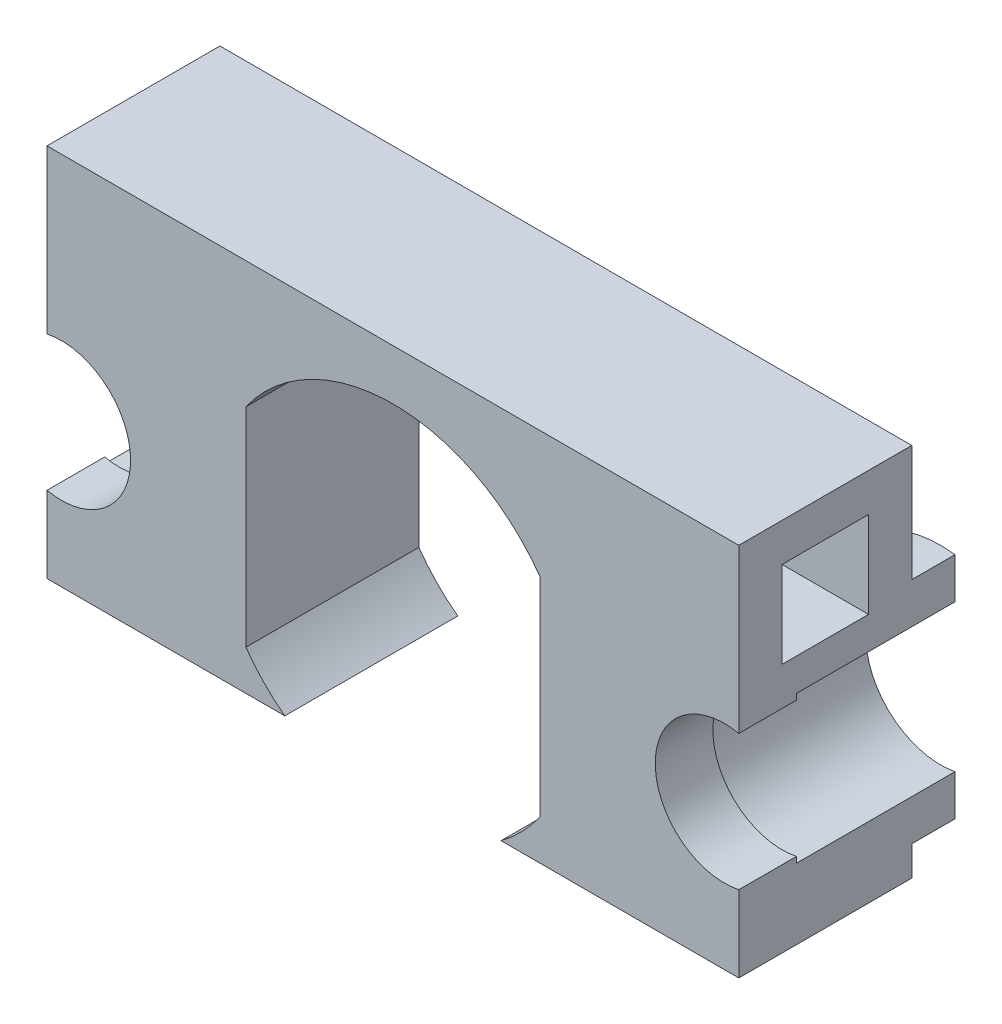
SolidWorks part; units mm, degrees
note: The reader was unsure of these and kept them because the rebuilt part matched: shared geometry of "Sketch17<2>", "Sketch19<3>".
ref_plane "Front Plane" through (0, 0, 0) normal (0, 0, 1) x (1, 0, 0)
ref_plane "Top Plane" through (0, 0, 0) normal (0, 1, 0) x (1, 0, 0)
ref_plane "Right Plane" through (0, 0, 0) normal (1, 0, 0) x (0, 0, -1)
sketch "Sketch1" plane through (0, 0, 0) normal (0, 0, 1) x (1, 0, 0)
  line L0 (-11.5, 0) -> (11.5, 0) construction
  line L1 (3.75, -5) -> (14.7, -5)
  line L2 (-14.7, -5) -> (-3.75, -5)
  line L3 (-14.7, -5) -> (-14.7, 8)
  line L4 (-14.7, 8) -> (14.7, 8)
  line L5 (14.7, -5) -> (14.7, 8)
  line L6 (-17.6832, -10.5909) -> (24.7009, -10.5909)
  line L7 (-24.9768, -7) -> (25.0232, -7) construction
  line L8 (-24.9768, -7) -> (-24.9768, -5) construction
  line L9 (-24.9768, -5) -> (-3.75, -5) construction
  line L10 (25.0232, -7) -> (25.0232, -5) construction
  line L11 (-24.9768, -7) -> (25.0232, -5) construction
  line L12 (-24.9768, -5) -> (25.0232, -7) construction
  line L13 (-5.1, -3.6128) -> (-5.1, 3.6128)
  line L14 (9, -3) -> (14, -3) construction
  line L15 (9, -3) -> (9, 3) construction
  line L16 (9, 3) -> (14, 3) construction
  line L17 (14, -3) -> (14, 3) construction
  line L18 (9, -3) -> (14, 3) construction
  line L19 (9, 3) -> (14, -3) construction
  line L20 (5.1, -3.6128) -> (5.1, 3.6128)
  line L21 (-5.1, -3.6128) -> (5.1, 3.6128) construction
  line L22 (-5.1, 3.6128) -> (5.1, -3.6128) construction
  line L23 (3.75, -5) -> (25.0232, -5) construction
  circle A0 centre (0, 0) radius 2 construction
  circle A1 centre (11.5, 0) radius 9.5 construction
  circle A2 centre (-11.5, 0) radius 9.5 construction
  circle A3 centre (11.5, 0) radius 10.5909 construction
  circle A4 centre (-11.5, 0) radius 10.5909 construction
  circle A5 centre (0, 0) radius 0.5
  circle A6 centre (-11.5, 0) radius 1
  circle A7 centre (11.5, 0) radius 1
  arc A8 (5.1, 3.6128) -> (-5.1, 3.6128) centre (0, 0) ccw
  arc A9 (-5.1, -3.6128) -> (-3.75, -5) centre (0, 0) ccw
  arc A10 (3.75, -5) -> (5.1, -3.6128) centre (0, 0) ccw
  point P13 (0, 0)
  point P17 (0, 8)
  point P18 (0.0232, -6)
  point P29 (3.5089, -10.5909)
  dimension "D1" = 4
  dimension "D2" = 19
  dimension "D5" = 1
  dimension "D6" = 2
  dimension "D9" = 12.5
  dimension "D3" = 13
  dimension "D4" = 2
  dimension "D7" = 5
  dimension "D8" = 6
  dimension "D10" = 10.2
  dimension "D11" = 8
  dimension "D12" = 3.2
extrude "Boss-Extrude1" add sketch "Sketch1" along normal blind 6 contours A10 L1 L5 L4 L3 L2 A9 L13 A8 L20 A7 A6
sketch "Sketch2" plane through (0, 0, 0) normal (0, 0, 1) x (1, 0, 0)
  circle A0 centre (-11.5, 0) radius 2.6
  circle A1 centre (11.5, 0) radius 2.6
  dimension "D1" = 5.2
extrude "Cut-Extrude1" cut sketch "Sketch2" along normal blind 6
sketch "Sketch3" plane through (0, 0, 0) normal (0, 0, 1) x (1, 0, 0)
  line L0 (-14.7, -5) -> (-3.75, -5) construction
  line L1 (-14.7, 8) -> (-22.3, 8)
  line L2 (-14.7, 8) -> (-14.7, -5)
  line L3 (-14.7, -5) -> (-22.3, -5)
  line L4 (-22.3, 8) -> (-22.3, -5)
  dimension "D1" = 7.6
extrude "Boss-Extrude2" add sketch "Sketch3" along normal blind 6
sketch "Sketch6" plane through (0, 0, 0) normal (0, 1, 0) x (1, 0, 0)
  line L0 (-22.3, -6) -> (-22.3, 0) construction
  line L1 (-22.3, -2) -> (-25.3, -2)
  line L2 (-22.3, -2) -> (-22.3, -4)
  line L3 (-22.3, -4) -> (-25.3, -4)
  line L4 (-25.3, -2) -> (-25.3, -4)
  line L5 (14.7, -6) -> (14.7, 0) construction
  line L6 (14.7, -2) -> (17.7, -2)
  line L7 (14.7, -2) -> (14.7, -4)
  line L8 (14.7, -4) -> (17.7, -4)
  line L9 (17.7, -2) -> (17.7, -4)
  point P12 (-22.3, -3)
  point P13 (-22.3, -3)
  dimension "D1" = 2
  dimension "D2" = 3
extrude "Boss-Extrude5" add sketch "Sketch6" along normal up to surface (13 mm away) from surface
sketch "Sketch10" plane through (0, 0, 6) normal (0, 0, 1) x (1, 0, 0)
  line L0 (14.7, 2.4) -> (14.7, -2.4)
  line L2 (14.7, -5) -> (14.7, 8) construction
  circle A0 centre (-11.5, 0) radius 2.6
  circle A1 centre (11.5, 0) radius 2.6
  circle A2 centre (-11.5, 0) radius 2.6 construction
  circle A3 centre (11.5, 0) radius 2.6 construction
  arc A4 (14.7, 2.4) -> (14.7, -2.4) centre (11.5, 0) ccw
  circle A5 centre (-11.5, 0) radius 4
  dimension "D1" = 8
extrude "Boss-Extrude6" add sketch "Sketch10" against normal blind 1.5 from surface at -6 starting at face at (-8.9, 0, 0)
sketch "Sketch12" plane through (0, 0, 0) normal (0, 0, -1) x (-1, 0, 0)
  circle A0 centre (-11.5, 0) radius 2.4
  circle A1 centre (11.5, 0) radius 2.4
  circle A2 centre (11.5, 0) radius 2.6
  circle A3 centre (-11.5, 0) radius 2.6
  circle A4 centre (-11.5, 0) radius 2.6 construction
  circle A5 centre (11.5, 0) radius 2.6 construction
  dimension "D1" = 4.8
extrude "Boss-Extrude7" add sketch "Sketch12" along normal blind 2 from surface at -6 starting at face at (-8.9, 0, 6)
sketch "Sketch13" plane through (0, -5, 0) normal (0, -1, 0) x (1, 0, 0)
  line L12 (-22.3, 6) -> (-3.75, 6) construction
  line L13 (-22.3, 0) -> (-16.3, 0)
  line L14 (-22.3, 0) -> (-22.3, 2)
  line L15 (-22.3, 2) -> (-20.8, 2)
  line L16 (-16.3, 0) -> (-16.3, 2)
  line L18 (-20.8, 2) -> (-20.8, 6)
  line L19 (-20.8, 6) -> (-17.8, 6)
  line L20 (-17.8, 2) -> (-17.8, 6)
  line L21 (-17.8, 2) -> (-16.3, 2)
  dimension "D1" = 6
  dimension "D2" = 3
  dimension "D3" = 2
extrude "Cut-Extrude2" cut sketch "Sketch13" against normal blind 7
sketch "Sketch14" plane through (0, 0, 0) normal (0, 0, -1) x (-1, 0, 0)
  line L0 (22.3, 8) -> (-14.7, 8) construction
  line L1 (20.8, 2) -> (17.8, 2)
  line L2 (20.8, 2) -> (20.8, 8)
  line L3 (20.8, 8) -> (17.8, 8)
  line L4 (17.8, 2) -> (17.8, 8)
  line L5 (17.8, 2) -> (17.8, -5) construction
extrude "Cut-Extrude3" cut sketch "Sketch14" against normal blind 2
sketch "Sketch15" plane through (0, 0, 0) normal (0, 0, 1) x (1, 0, 0)
  line L0 (-17.8, 8) -> (14.7, 8) construction
  line L1 (-12, -5) -> (-12.2, -5)
  line L2 (-12, -5) -> (-12, 8)
  line L3 (-12, 8) -> (-12.2, 8)
  line L4 (-12.2, -5) -> (-12.2, 8)
  line L5 (-12, -5) -> (-12.2, 8) construction
  line L6 (-12, 8) -> (-12.2, -5) construction
  line L7 (3.75, -5) -> (14.7, -5) construction
  line L8 (12, -5) -> (12.2, -5)
  line L9 (12, -5) -> (12, 8)
  line L10 (12, 8) -> (12.2, 8)
  line L11 (12.2, -5) -> (12.2, 8)
  line L12 (12, -5) -> (12.2, 8) construction
  line L13 (12, 8) -> (12.2, -5) construction
  circle A0 centre (-11.5, 0) radius 2.4 construction
  circle A1 centre (11.5, 0) radius 2.4 construction
  point P0 (-12.1, 1.5)
  point P7 (12.1, 1.5)
  dimension "D1" = 0.2
  dimension "D2" = 0.5
  dimension "D3" = 0.5
extrude "Cut-Extrude5" cut sketch "Sketch15" against normal mid plane 15
sketch "Sketch16" plane through (12, 0, 0) normal (1, 0, 0) x (0, 0, -1)
  line L0 (0, 8) -> (-6, 2.3473) construction
  line L2 (-1.5, 3.6737) -> (-4.5, 3.6737)
  line L3 (-1.5, 3.6737) -> (-1.5, 6.6737)
  line L4 (-1.5, 6.6737) -> (-4.5, 6.6737)
  line L5 (-4.5, 3.6737) -> (-4.5, 6.6737)
  line L6 (-1.5, 3.6737) -> (-4.5, 6.6737) construction
  line L7 (-1.5, 6.6737) -> (-4.5, 3.6737) construction
  point P4 (-3, 5.1737)
  dimension "D1" = 3
extrude "Cut-Extrude6" cut sketch "Sketch16" against normal blind 3
mirror "Mirror1" about plane through (0, 0, 0) normal (1, 0, 0) of "Cut-Extrude6"
sketch "Sketch17" plane through (-12.2, 0, 0) normal (1, 0, 0) x (0, 0, -1)
  line L0 (-4.5, 6.6737) -> (-1.5, 3.6737) construction
  line L2 (-4.4, 3.7737) -> (-1.6, 3.7737)
  line L3 (-4.4, 3.7737) -> (-4.4, 6.5737)
  line L4 (-4.4, 6.5737) -> (-1.6, 6.5737)
  line L5 (-1.6, 3.7737) -> (-1.6, 6.5737)
  line L6 (-4.4, 3.7737) -> (-1.6, 6.5737) construction
  line L7 (-4.4, 6.5737) -> (-1.6, 3.7737) construction
  point P4 (-3, 5.1737)
  dimension "D1" = 2.8
extrude "Boss-Extrude9" add sketch "Sketch17" along normal blind 3
extrude "Boss-Extrude10" add sketch "Sketch17<2>" against normal blind 3 from surface at 24.4 starting at face at (12.2, -3.4345, 2.125)
sketch "Sketch17<2>" plane through (-12.2, 0, 0) normal (1, 0, 0) x (0, 0, -1) same geometry as "Sketch17"
sketch "Sketch18" plane through (0, 0, 0) normal (0, 0, 1) x (1, 0, 0)
  line L1 (12, 8) -> (17.7, 8)
  line L2 (12, 8) -> (12, -5)
  line L3 (12, -5) -> (17.7, -5)
  line L4 (17.7, 8) -> (17.7, -5)
  line L5 (-12, 8) -> (-25.3, 8)
  line L6 (-12, 8) -> (-12, -5)
  line L7 (-12, -5) -> (-25.3, -5)
  line L8 (-25.3, 8) -> (-25.3, -5)
extrude "Cut-Extrude7" cut sketch "Sketch18" against normal mid plane 18
sketch "Sketch19" plane through (12, 0, 0) normal (1, 0, 0) x (0, 0, -1)
  line L1 (-4.5, 6.6737) -> (-1.5, 6.6737)
  line L2 (-4.5, 6.6737) -> (-4.5, 3.6737)
  line L3 (-4.5, 3.6737) -> (-1.5, 3.6737)
  line L4 (-1.5, 6.6737) -> (-1.5, 3.6737)
extrude "Cut-Extrude8" cut sketch "Sketch19" against normal blind 3
extrude "Cut-Extrude10" cut sketch "Sketch19<3>" along normal blind 3 from surface at -24 starting at face at (-12, 5.1737, 3)
sketch "Sketch19<3>" plane through (12, 0, 0) normal (1, 0, 0) x (0, 0, -1) same geometry as "Sketch19"
